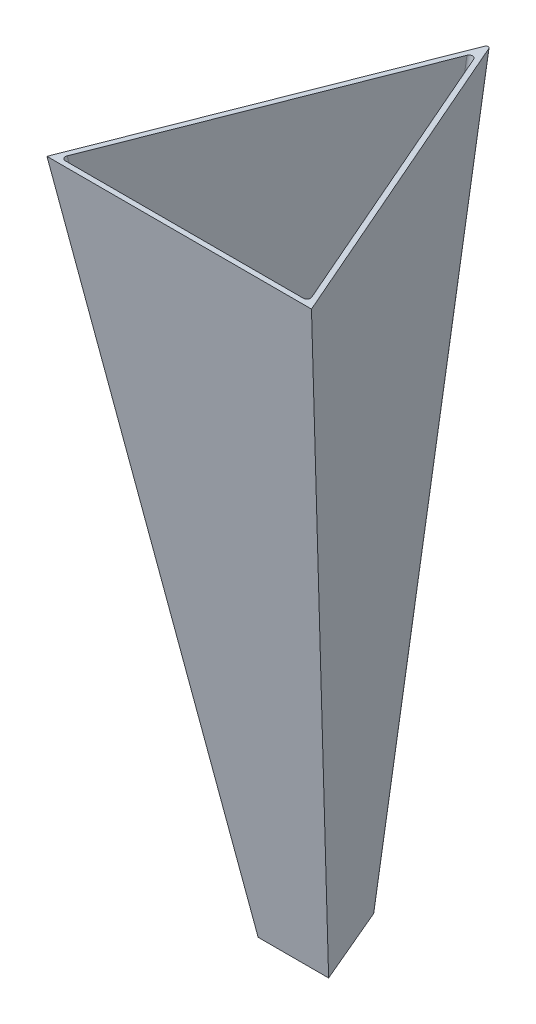
SolidWorks part; units mm, degrees
ref_plane "Front Plane" through (0, 0, 0) normal (0, 0, 1) x (1, 0, 0)
ref_plane "Top Plane" through (0, 0, 0) normal (0, 1, 0) x (1, 0, 0)
ref_plane "Right Plane" through (0, 0, 0) normal (1, 0, 0) x (0, 0, -1)
sketch "Sketch1" plane through (0, 0, 0) normal (1, 0, 0) x (0, 0, -1)
  line L0 (0, 0) -> (0, 5) construction
  dimension "D1" = 5
ref_plane "Plane1" through (0, 5, 0) normal (0, 1, 0) x (1, 0, 0)
sketch "Sketch3" plane through (0, 5, 0) normal (0, 1, 0) x (1, 0, 0)
  line L0 (0, 0) -> (8.5, 0) construction
  line L1 (8.5, 0) -> (4.25, 10) construction
  line L2 (4.25, 10) -> (0, 0) construction
  line L3 (4.25, 0) -> (4.25, 10) construction
  line L4 (4.25, 10.8948) -> (-0.529, -0.35)
  line L5 (-0.529, -0.35) -> (9.029, -0.35)
  line L6 (9.029, -0.35) -> (4.25, 10.8948)
  line L7 (4.25, 9.1052) -> (0.529, 0.35)
  line L8 (0.529, 0.35) -> (7.971, 0.35)
  line L9 (7.971, 0.35) -> (4.25, 9.1052)
  dimension "D1" = 8.5
  dimension "D2" = 10
  dimension "D3" = 0.35
  dimension "D4" = 0.35
sketch3d "3DSketch3"
  line L0 (0, -25, 0) -> (4.25, -25, 0) construction
  line L1 (0, 0, 0) -> (0, 5, 0) construction
  line L2 (4.25, -25, 0) -> (4.25, -25, -5) construction
  line L4 (4.25, -25, -5) -> (8.5, 5, 0) construction
  line L5 (8.5, 5, 0) -> (21.6627, 97.9129, 15.4855) construction
  line L6 (4.25, -25, -5) -> (4.25, 5, -10) construction
  line L9 (4.25, 5, -10) -> (4.25, 98.8157, -25.636) construction
  line L10 (4.25, -25, -5) -> (0, 5, 0) construction
  line L11 (0, 5, 0) -> (-13.1627, 97.9129, 15.4855) construction
  line L16 (0, 0, 0) -> (0, -25, 0) construction
  dimension "D1" = 25
  dimension "D2" = 4.25
  dimension "D4" = 5
  dimension "D3" = 100
ref_plane "Plane2" through (0, 98.2056, 2.156) normal (0, -0.9998, -0.0219) x (-0.9996, -0.0006, 0.0271)
sketch "Sketch4" plane through (0, 98.2056, 2.156) normal (0, -0.9998, -0.0219) x (-0.9996, -0.0006, 0.0271)
  line L0 (-5.0014, 27.6733) -> (13.519, -12.9713) construction
  line L1 (13.519, -12.9713) -> (-21.2936, -13.9146) construction
  line L2 (-21.2936, -13.9146) -> (-5.0014, 27.6733) construction
  line L3 (-5.0257, 28.5708) -> (14.0565, -13.3069)
  line L4 (14.0565, -13.3069) -> (-21.8122, -14.2788)
  line L5 (-21.8122, -14.2788) -> (-5.0257, 28.5708)
  line L6 (-4.9771, 26.7759) -> (12.9814, -12.6357)
  line L7 (12.9814, -12.6357) -> (-20.775, -13.5504)
  line L8 (-20.775, -13.5504) -> (-4.9771, 26.7759)
  dimension "D1" = 0.35
  dimension "D2" = 0.35
loft "Loft1" add section "Sketch3" section "Sketch4" connector at (4.25, 5, -10.8948) connector at (4.25, 98.8354, -26.5335)
loft "Cut-Loft1" cut section "Sketch3<411>" section "Sketch4<174>" connector at (4.25, 5, -9.1052) connector at (4.25, 98.796, -24.7384)
sketch "Sketch3<411>" plane through (0, 5, 0) normal (0, 1, 0) x (1, 0, 0) same geometry as "Sketch3"
sketch "Sketch4<174>" plane through (0, 98.2056, 2.156) normal (0, -0.9998, -0.0219) x (-0.9996, -0.0006, 0.0271) same geometry as "Sketch4"
fillet "Fillet1" radius 0.5 3 edges
sketch3d "3DSketch5"
  line L0 (4.25, -25, -5) -> (0, 5, 0) construction
  line L1 (8.5, 5, 0) -> (4.25, -25, -5) construction
fillet "Fillet2" [suppressed] radius 0.2
fillet "Fillet3" radius 0.3 1 edges
